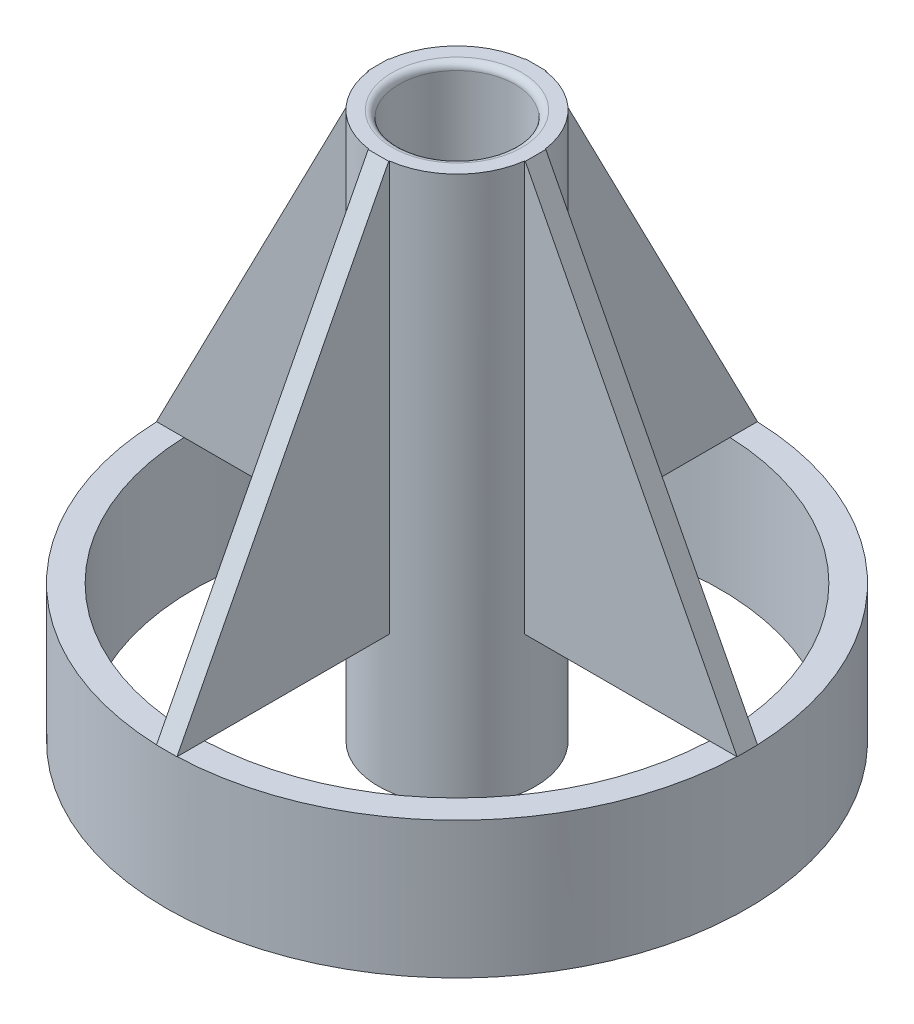
SolidWorks part; units mm, degrees
ref_plane "Front Plane" through (0, 0, 0) normal (0, 0, 1) x (1, 0, 0)
ref_plane "Top Plane" through (0, 0, 0) normal (0, 1, 0) x (1, 0, 0)
ref_plane "Right Plane" through (0, 0, 0) normal (1, 0, 0) x (0, 0, -1)
sketch "Sketch1" plane through (0, 0, 0) normal (0, 1, 0) x (1, 0, 0)
  circle A0 centre (0, 0) radius 19.25
  circle A1 centre (0, 0) radius 21.25
  dimension "D1" = 38.5
  dimension "D2" = 2
extrude "Boss-Extrude1" add sketch "Sketch1" along normal blind 10
sketch "Sketch2" plane through (0, 10, 0) normal (0, 1, 0) x (1, 0, 0)
  circle A0 centre (0, 0) radius 4.25
  circle A1 centre (0, 0) radius 5.75
  dimension "D1" = 8.5
  dimension "D2" = 1.5
extrude "Boss-Extrude2" add sketch "Sketch2" along normal blind 30 separate body
sketch "Sketch3" plane through (0, 0, 0) normal (0, 0, 1) x (1, 0, 0)
  line L0 (-21.25, 10) -> (-5.75, 40)
  line L1 (-5.75, 40) -> (-4.25, 40)
  line L2 (-4.25, 40) -> (-4.25, 10)
  line L3 (-4.25, 10) -> (-5.75, 10)
  line L4 (21.25, 10) -> (-21.25, 10) construction
  line L5 (-5.75, 40) -> (-5.75, 10) construction
  line L9 (-5.75, 10) -> (-21.25, 10)
extrude "Boss-Extrude3" add sketch "Sketch3" along normal mid plane 1.5
pattern_circular "CirPattern1" count 4 over 360 about axis through (0, 40, 0) along (0, -1, 0) of "Boss-Extrude3"
fillet "Fillet1" radius 0.5 1 edges at (0, 40, 4.25)
sketch "Sketch4" plane through (0, 10, 0) normal (0, -1, 0) x (1, 0, 0)
  circle A0 centre (0, 0) radius 5.75
  circle A1 centre (0, 0) radius 4.25
extrude "Boss-Extrude4" add sketch "Sketch4" along normal blind 10
fillet "Fillet2" radius 0.5 1 edges at (0, 0, -4.25)
